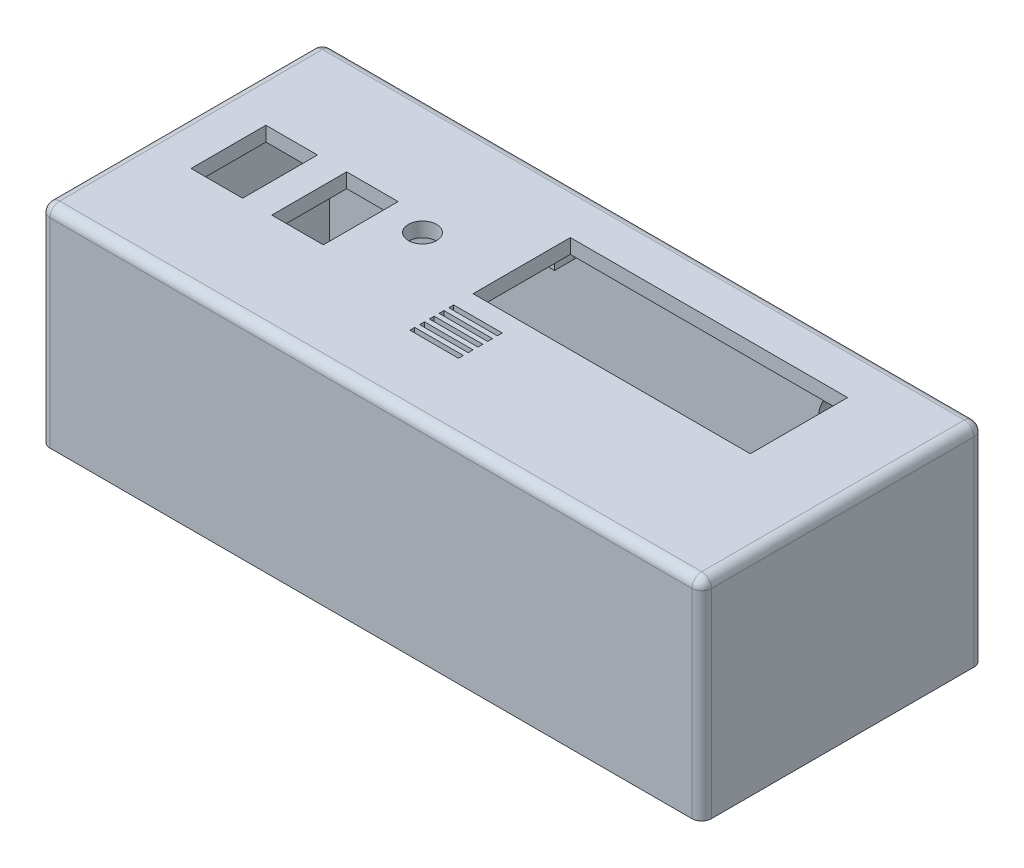
SolidWorks part; units mm, degrees
other "Markup1"
sketch "Sketch10" plane through (0, 3.81, -80.01) normal (-0.0664, 0.6011, -0.7964) x (-0.8607, 0.3692, 0.3504)
ref_plane "Front Plane" through (0, 0, 0) normal (0, 0, 1) x (1, 0, 0)
ref_plane "Top Plane" through (0, 0, 0) normal (0, 1, 0) x (1, 0, 0)
ref_plane "Right Plane" through (0, 0, 0) normal (1, 0, 0) x (0, 0, -1)
sketch "Sketch1" plane through (0, 0, 0) normal (0, 1, 0) x (1, 0, 0)
  line L1 (0, 73.66) -> (172.72, 73.66)
  line L2 (0, 73.66) -> (0, 0)
  line L3 (0, 0) -> (172.72, 0)
  line L4 (172.72, 73.66) -> (172.72, 0)
  line L5 (77.47, 60.96) -> (149.86, 60.96)
  line L6 (77.47, 60.96) -> (77.47, 35.56)
  line L7 (77.47, 35.56) -> (149.86, 35.56)
  line L8 (149.86, 60.96) -> (149.86, 35.56)
  line L9 (12.319, 46.609) -> (25.781, 46.609)
  line L10 (12.319, 46.609) -> (12.319, 27.051)
  line L11 (12.319, 27.051) -> (25.781, 27.051)
  line L12 (25.781, 46.609) -> (25.781, 27.051)
  line L13 (33.401, 46.609) -> (46.863, 46.609)
  line L14 (33.401, 46.609) -> (33.401, 27.051)
  line L15 (33.401, 27.051) -> (46.863, 27.051)
  line L16 (46.863, 46.609) -> (46.863, 27.051)
  circle A3 centre (57.023, 42.799) radius 3.683
  dimension "D8" = 19.558
  dimension "D6" = 13.462
  dimension "D9" = 7.62
  dimension "D10" = 10.16
  dimension "D12" = 27.051
  dimension "D1" = 172.72
  dimension "D2" = 73.66
  dimension "D3" = 25.4
  dimension "D4" = 72.39
  dimension "D5" = 22.86
  dimension "D7" = 0
  dimension "D11" = 12.7
  dimension "D13" = 0
  dimension "D19" = 3.81
extrude "Boss-Extrude1" add sketch "Sketch1" along normal blind 3.81
sketch "Sketch2" plane through (0, 0, 0) normal (0, -1, 0) x (1, 0, 0)
  line L0 (77.47, -48.26) -> (149.86, -48.26) construction
  line L1 (77.47, -60.96) -> (77.47, -35.56) construction
  line L2 (149.86, -35.56) -> (149.86, -60.96) construction
  line L3 (113.665, -35.56) -> (113.665, -60.96) construction
  line L4 (77.47, -35.56) -> (149.86, -35.56) construction
  line L5 (149.86, -60.96) -> (77.47, -60.96) construction
  line L6 (70.1675, -37.465) -> (75.2475, -37.465)
  line L7 (75.2475, -37.465) -> (75.2475, -32.385)
  line L8 (70.1675, -59.055) -> (75.2475, -59.055)
  line L9 (75.2475, -59.055) -> (75.2475, -64.135)
  line L10 (152.0825, -32.385) -> (152.0825, -37.465)
  line L11 (152.0825, -37.465) -> (157.1625, -37.465)
  line L12 (152.0825, -64.135) -> (152.0825, -59.055)
  line L13 (152.0825, -59.055) -> (157.1625, -59.055)
  arc A0 (75.2475, -32.385) -> (70.1675, -37.465) centre (70.1675, -32.385) ccw
  arc A1 (70.1675, -59.055) -> (75.2475, -64.135) centre (70.1675, -64.135) ccw
  arc A2 (152.0825, -64.135) -> (157.1625, -59.055) centre (157.1625, -64.135) ccw
  arc A3 (157.1625, -37.465) -> (152.0825, -32.385) centre (157.1625, -32.385) ccw
  dimension "D2" = 10.16
  dimension "D5" = 0
  dimension "D6" = 15.875
  dimension "D7" = 31.75
  dimension "D8" = 15.875
  dimension "D9" = 86.995
  dimension "D10" = 43.4975
  dimension "D11" = 31.75
  dimension "D12" = 0
extrude "Boss-Extrude2" add sketch "Sketch2" along normal blind 3.81
sketch "Sketch3" plane through (0, -3.81, 0) normal (0, -1, 0) x (1, 0, 0)
  circle A0 centre (70.1675, -32.385) radius 1.9685
  circle A1 centre (70.1675, -64.135) radius 1.9685
  circle A2 centre (157.1625, -64.135) radius 1.9685
  circle A3 centre (157.1625, -32.385) radius 1.9685
  dimension "D1" = 3.937
extrude "Cut-Extrude1" cut sketch "Sketch3" against normal blind 6.35
sketch "Sketch4" plane through (0, 0, 0) normal (0, -1, 0) x (1, 0, 0)
  line L1 (0, 0) -> (172.72, 0)
  line L2 (0, 0) -> (0, -73.66)
  line L3 (0, -73.66) -> (172.72, -73.66)
  line L4 (172.72, 0) -> (172.72, -73.66)
  line L5 (3.81, -3.81) -> (168.91, -3.81)
  line L6 (3.81, -3.81) -> (3.81, -71.755)
  line L7 (3.81, -71.755) -> (168.91, -71.755)
  line L8 (168.91, -3.81) -> (168.91, -71.755)
  dimension "D1" = 3.81
  dimension "D2" = 3.81
  dimension "D3" = 3.81
  dimension "D4" = 1.905
extrude "Boss-Extrude4" add sketch "Sketch4" along normal blind 50.8
fillet "Fillet1" radius 2.54 8 edges at (86.36, 3.81, -73.66) (172.72, -23.495, -73.66) (172.72, 3.81, -36.83) (172.72, -23.495, 0) (86.36, 3.81, 0) (0, 3.81, -36.83) (0, -23.495, -73.66) (0, -23.495, 0)
sketch "Sketch5" plane through (0, -50.8, 0) normal (0, -1, 0) x (1, 0, 0)
  line L0 (3.81, -3.81) -> (3.81, -71.755) construction
  line L1 (3.81, -3.81) -> (13.97, -3.81)
  line L2 (3.81, -3.81) -> (3.81, -13.97)
  line L3 (3.81, -13.97) -> (13.97, -13.97)
  line L4 (13.97, -3.81) -> (13.97, -13.97)
  line L5 (3.81, -61.595) -> (13.97, -61.595)
  line L6 (3.81, -61.595) -> (3.81, -71.755)
  line L7 (3.81, -71.755) -> (13.97, -71.755)
  line L8 (13.97, -61.595) -> (13.97, -71.755)
  line L9 (3.81, -71.755) -> (168.91, -71.755) construction
  line L10 (168.91, -71.755) -> (168.91, -3.81) construction
  line L15 (168.91, -3.81) -> (3.81, -3.81) construction
  line L16 (158.75, -3.81) -> (168.91, -3.81)
  line L17 (158.75, -3.81) -> (158.75, -13.97)
  line L18 (158.75, -13.97) -> (168.91, -13.97)
  line L19 (168.91, -3.81) -> (168.91, -13.97)
  line L20 (168.91, -71.755) -> (168.91, -3.81) construction
  line L21 (153.035, -71.755) -> (142.875, -71.755)
  line L22 (153.035, -71.755) -> (153.035, -61.595)
  line L23 (153.035, -61.595) -> (142.875, -61.595)
  line L24 (142.875, -71.755) -> (142.875, -61.595)
  point P27 (168.91, -8.89)
  dimension "D1" = 10.16
  dimension "D2" = 10.16
  dimension "D3" = 10.16
  dimension "D4" = 10.16
  dimension "D5" = 10.16
  dimension "D7" = 15.875
extrude "Boss-Extrude5" add sketch "Sketch5" against normal blind 6.35
fillet "Fillet2" radius 2.54 5 edges at (153.035, -47.625, -61.595) (142.875, -47.625, -61.595) (158.75, -47.625, -13.97) (13.97, -47.625, -13.97) (13.97, -47.625, -61.595)
sketch "Sketch6" plane through (0, -50.8, 0) normal (0, -1, 0) x (1, 0, 0)
  line L0 (11.43, -61.595) -> (3.81, -61.595) construction
  line L1 (13.97, -71.755) -> (13.97, -64.135) construction
  line L2 (3.81, -13.97) -> (11.43, -13.97) construction
  line L3 (13.97, -11.43) -> (13.97, -3.81) construction
  line L4 (158.75, -3.81) -> (158.75, -11.43) construction
  line L5 (161.29, -13.97) -> (168.91, -13.97) construction
  line L6 (150.495, -61.595) -> (145.415, -61.595) construction
  line L7 (142.875, -64.135) -> (142.875, -71.755) construction
  circle A0 centre (8.89, -66.675) radius 1.9685
  circle A1 centre (8.89, -8.89) radius 1.9685
  circle A2 centre (163.83, -8.89) radius 1.9685
  circle A3 centre (147.955, -66.675) radius 1.9685
  dimension "D2" = 3.937
  dimension "D5" = 5.08
  dimension "D6" = 5.08
  dimension "D7" = 5.08
  dimension "D8" = 5.08
  dimension "D9" = 5.08
  dimension "D10" = 5.08
  dimension "D11" = 5.08
  dimension "D12" = 5.08
extrude "Cut-Extrude2" cut sketch "Sketch6" against normal blind 6.35
sketch "Sketch7" plane through (0, 3.81, 0) normal (0, 1, 0) x (1, 0, 0)
  line L0 (77.47, 35.56) -> (149.86, 35.56) construction
  line L1 (77.47, 30.48) -> (90.17, 30.48)
  line L2 (77.47, 30.48) -> (77.47, 29.21)
  line L3 (77.47, 29.21) -> (90.17, 29.21)
  line L4 (90.17, 30.48) -> (90.17, 29.21)
  line L5 (77.47, 27.94) -> (90.17, 27.94)
  line L6 (77.47, 27.94) -> (77.47, 26.67)
  line L7 (77.47, 26.67) -> (90.17, 26.67)
  line L8 (90.17, 27.94) -> (90.17, 26.67)
  line L9 (77.47, 25.4) -> (90.17, 25.4)
  line L10 (77.47, 25.4) -> (77.47, 24.13)
  line L11 (77.47, 24.13) -> (90.17, 24.13)
  line L12 (90.17, 25.4) -> (90.17, 24.13)
  line L13 (77.47, 22.86) -> (90.17, 22.86)
  line L14 (77.47, 22.86) -> (77.47, 21.59)
  line L15 (77.47, 21.59) -> (90.17, 21.59)
  line L16 (90.17, 22.86) -> (90.17, 21.59)
  line L21 (77.47, 60.96) -> (77.47, 35.56) construction
  line L22 (77.47, 20.32) -> (90.17, 20.32)
  line L23 (77.47, 20.32) -> (77.47, 19.05)
  line L24 (77.47, 19.05) -> (90.17, 19.05)
  line L25 (90.17, 20.32) -> (90.17, 19.05)
  dimension "D1" = 12.7
  dimension "D2" = 1.27
  dimension "D3" = 5.08
  dimension "D5" = 0
  dimension "D4" = 5
extrude "Cut-Extrude3" cut sketch "Sketch7" against normal blind 3.81
sketch "Sketch8" plane through (0, 0, -73.66) normal (0, 0, -1) x (-1, 0, 0)
  line L0 (-2.54, 1.27) -> (-170.18, 1.27) construction
  line L1 (-170.18, 1.27) -> (-170.18, -50.8) construction
  circle A0 centre (-140.97, -15.621) radius 9.525
  dimension "D1" = 19.05
  dimension "D2" = 16.891
  dimension "D3" = 29.21
extrude "Cut-Extrude4" cut sketch "Sketch8" against normal blind 2.54
sketch "Sketch9" plane through (0, 0, -73.66) normal (0, 0, -1) x (-1, 0, 0)
  circle A0 centre (-140.97, -15.621) radius 9.525
  circle A1 centre (-140.97, -15.621) radius 16.51
  dimension "D1" = 19.05
  dimension "D2" = 33.02
extrude "Boss-Extrude6" add sketch "Sketch9" along normal blind 6.35
chamfer "Chamfer1" distance 6.35 angle 45 1 edges at (124.46, -15.621, -80.01)
